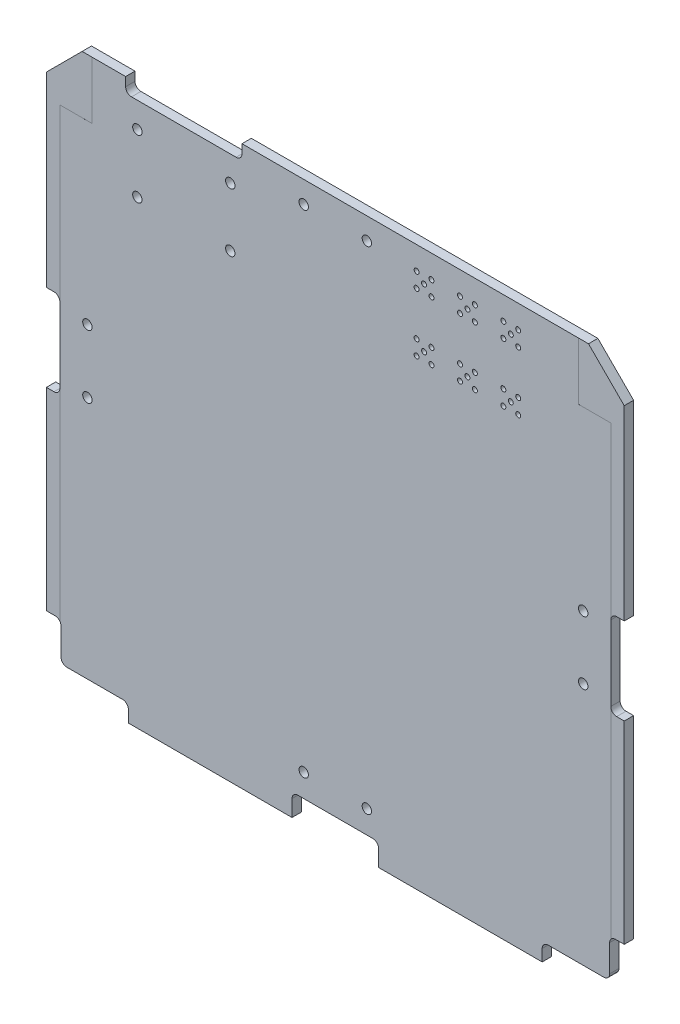
SolidWorks part; units mm, degrees
material "Oshpark board"
ref_plane "Front Plane" through (0, 0, 0) normal (0, 0, 1) x (1, 0, 0)
ref_plane "Top Plane" through (0, 0, 0) normal (0, 1, 0) x (1, 0, 0)
ref_plane "Right Plane" through (0, 0, 0) normal (1, 0, 0) x (0, 0, -1)
ref_plane "Plane4" through (0, 0, -0.0125) normal (0, 0, -1) x (-1, 0, 0)
sketch "Sketch1" plane through (0, 0, -0.0125) normal (0, 0, -1) x (-1, 0, 0)
  line L0 (35.3, -50) -> (35.3, -48)
  line L1 (36.3, -47) -> (45.8, -47)
  line L2 (46.8, -46) -> (46.8, -41.4)
  line L3 (47.8, -40.4) -> (49.3, -40.4)
  line L4 (49.3, -40.4) -> (49.3, 39.2)
  line L5 (49.3, 39.2) -> (43.2, 45.3)
  line L6 (43.2, 45.3) -> (35.5, 45.3)
  line L7 (35.5, 45.3) -> (35.5, 43.8) construction
  line L8 (34.5, 42.8) -> (4.5, 42.8) construction
  line L9 (3.5, 43.8) -> (3.5, 45.3) construction
  line L10 (3.5, 45.3) -> (-43.2, 45.3)
  line L11 (-43.2, 45.3) -> (-49.3, 39.2)
  line L12 (-49.3, 39.2) -> (-49.3, -40.4)
  line L13 (-49.3, -40.4) -> (-47.8, -40.4)
  line L14 (-46.8, -41.4) -> (-46.8, -46)
  line L15 (-45.8, -47) -> (-36.3, -47)
  line L16 (-35.3, -48) -> (-35.3, -50)
  line L17 (-35.3, -50) -> (35.3, -50)
  line L18 (0, -50) -> (0, 45.3) construction
  line L19 (19.5, 42.8) -> (19.5, 25.5258) construction
  line L20 (-13.87, 41.37) -> (-16.41, 38.83) construction
  line L21 (-21.27, 41.37) -> (-23.81, 38.83) construction
  line L22 (-28.67, 41.37) -> (-31.21, 38.83) construction
  line L23 (35.5, 45.3) -> (3.5, 45.3)
  arc A0 (35.3, -48) -> (36.3, -47) centre (36.3, -48) cw
  arc A1 (45.8, -47) -> (46.8, -46) centre (45.8, -46) ccw
  arc A2 (46.8, -41.4) -> (47.8, -40.4) centre (47.8, -41.4) cw
  arc A3 (35.5, 43.8) -> (34.5, 42.8) centre (34.5, 43.8) cw construction
  arc A4 (4.5, 42.8) -> (3.5, 43.8) centre (4.5, 43.8) cw construction
  arc A5 (-47.8, -40.4) -> (-46.8, -41.4) centre (-47.8, -41.4) cw
  arc A6 (-46.8, -46) -> (-45.8, -47) centre (-45.8, -46) ccw
  arc A7 (-36.3, -47) -> (-35.3, -48) centre (-36.3, -48) cw
  circle A8 centre (-21.27, 41.37) radius 0.425
  circle A9 centre (-23.81, 41.37) radius 0.425
  circle A10 centre (-22.54, 40.1) radius 0.425
  circle A11 centre (-13.87, 41.37) radius 0.425
  circle A12 centre (-23.81, 38.83) radius 0.425
  circle A13 centre (-16.41, 41.37) radius 0.425
  circle A14 centre (-15.14, 40.1) radius 0.425
  circle A15 centre (-21.27, 38.83) radius 0.425
  circle A16 centre (-28.67, 41.37) radius 0.425
  circle A17 centre (-31.21, 41.37) radius 0.425
  circle A18 centre (-16.41, 38.83) radius 0.425
  circle A19 centre (-29.94, 40.1) radius 0.425
  circle A20 centre (-31.21, 38.83) radius 0.425
  circle A21 centre (-28.67, 38.83) radius 0.425
  circle A22 centre (33.775, 38.54) radius 0.8 construction
  circle A23 centre (5.225, 38.54) radius 0.8 construction
  circle A24 centre (-13.87, 38.83) radius 0.425
  point P35 (-15.14, 40.1)
  dimension "D7" = 2.5
  dimension "D8" = 1.6
  dimension "D9" = 14.275
  dimension "D10" = 4.26
  dimension "D11" = 1
  dimension "D12" = 1
  dimension "D13" = 1
  dimension "D14" = 1
  dimension "D15" = 1
  dimension "D16" = 1
  dimension "D17" = 1
  dimension "D18" = 1
  dimension "D26" = 0.85
  dimension "D1" = 98.6
  dimension "D2" = 95.3
  dimension "D3" = 14
  dimension "D4" = 9.6
  dimension "D5" = 2.5
  dimension "D6" = 3
  dimension "D19" = 14
  dimension "D20" = 2.5
  dimension "D21" = 6.1
  dimension "D22" = 6.1
  dimension "D23" = 32
  dimension "D24" = 2.54
  dimension "D25" = 2.54
  dimension "D28" = 7.4
  dimension "D29" = 3.93
  dimension "D30" = 35.43
  dimension "D31" = 45
  dimension "D32" = 45
  dimension "D33" = 29.8
  dimension "D34" = 50
  dimension "D27" = 3
extrude "Boss-Extrude1" add sketch "Sketch1" against normal blind 1.6
sketch "thermalContacts_lower" plane through (0, 0, -0.0125) normal (0, 0, -1) x (-1, 0, 0)
  line L3 (47, 35.5) -> (47, -41.5)
  line L4 (41.5, 35.5) -> (41.5, 41.5)
  line L5 (41.5, 35.5) -> (47, 35.5)
  line L9 (-47, 35.5) -> (-47, -41.5)
  line L10 (-41.5, 35.5) -> (-47, 35.5)
  line L11 (-41.5, 35.5) -> (-41.5, 41.5)
  line L14 (-41.5, 41.5) -> (-41.5, 47)
  line L18 (41.5, 41.5) -> (41.5, 47)
  line L19 (-49.3, 39.2) -> (-49.3, -40.4) construction
  line L20 (47, -41.5) -> (59.8273, -41.5)
  line L21 (59.8273, -41.5) -> (59.8273, 47)
  line L22 (-56.1922, 47) -> (-41.5, 47)
  line L23 (41.5, 47) -> (59.8273, 47)
  line L24 (-56.1922, 47) -> (-56.1922, -41.5)
  line L25 (-47, -41.5) -> (-56.1922, -41.5)
  line L26 (49.3, -40.4) -> (49.3, 39.2) construction
  line L27 (-35.3, -50) -> (35.3, -50) construction
  line L28 (43.2, 45.3) -> (-43.2, 45.3) construction
  dimension "D1" = 2.3
  dimension "D2" = 8.5
  dimension "D3" = 1.7
  dimension "D4" = 7.8
  dimension "D5" = 9.8
  dimension "D6" = 8.5
  dimension "D7" = 2.3
  dimension "D8" = 9.8
  dimension "D9" = 7.8
  dimension "D10" = 1.7
sketch "thermalContacts_upper" plane through (0, 0, 1.5875) normal (0, 0, 1) x (1, 0, 0)
  line L3 (-47, 35.5) -> (-47, -41.5)
  line L4 (-41.5, 35.5) -> (-41.5, 41.5)
  line L5 (-41.5, 35.5) -> (-47, 35.5)
  line L9 (47, 35.5) -> (47, -41.5)
  line L10 (41.5, 35.5) -> (47, 35.5)
  line L11 (41.5, 35.5) -> (41.5, 41.5)
  line L14 (41.5, 41.5) -> (41.5, 47)
  line L15 (41.5, 41.5) -> (49.5, 41.5) construction
  line L18 (-41.5, 41.5) -> (-41.5, 47)
  line L19 (-41.5, 41.5) -> (-49.5, 41.5) construction
  line L20 (47, -41.5) -> (59.8273, -41.5)
  line L21 (59.8273, -41.5) -> (59.8273, 47)
  line L22 (59.8273, 47) -> (41.5, 47)
  line L23 (-41.5, 47) -> (-56.1922, 47)
  line L24 (-56.1922, 47) -> (-56.1922, -41.5)
  line L25 (-56.1922, -41.5) -> (-47, -41.5)
pattern_linear "LPattern2" count 2 spacing 10 along (0, -1, 0) of face at (14.295, 41.37, 1.5875) of face at (14.295, 38.83, 1.5875) of face at (15.565, 40.1, 1.5875) of face at (16.835, 38.83, 1.5875) of face at (21.695, 41.37, 1.5875) of face at (21.695, 38.83, 1.5875) of face at (22.965, 40.1, 1.5875) of face at (24.235, 38.83, 1.5875) of face at (24.235, 41.37, 1.5875) of face at (16.835, 41.37, 1.5875) of face at (29.095, 41.37, 1.5875) of face at (29.095, 38.83, 1.5875) of face at (30.365, 40.1, 1.5875) of face at (31.635, 38.83, 1.5875) of face at (31.635, 41.37, 1.5875)
extrude "slotFootprints_REF" cut sketch "thermalContacts_lower" against normal blind 0.0001
extrude "slotFootprints" cut sketch "thermalContacts_upper" against normal blind 0.0001
sketch "Sketch2" plane through (0, 0, 1.5875) normal (0, 0, 1) x (1, 0, 0)
  line L1 (-41.5, 45.3) -> (41.5, 45.3) construction
  line L2 (-49.3, -40.4) -> (-49.3, 39.2) construction
  line L3 (-35.775, 45.3) -> (-35.775, 43.8)
  line L4 (-41.5, 45.3) -> (41.5, 45.3) construction
  line L5 (-34.775, 42.8) -> (-16.925, 42.8)
  line L6 (-15.925, 43.8) -> (-15.925, 45.3)
  line L7 (-15.925, 45.3) -> (-35.775, 45.3)
  arc A1 (-16.925, 42.8) -> (-15.925, 43.8) centre (-16.925, 43.8) ccw
  arc A2 (-35.775, 43.8) -> (-34.775, 42.8) centre (-34.775, 43.8) ccw
  circle A3 centre (-33.775, 38.4723) radius 0.8
  circle A4 centre (-17.925, 38.4723) radius 0.8
  circle A5 centre (-17.925, 28.4723) radius 0.8
  circle A6 centre (-33.775, 28.4723) radius 0.8
  dimension "D2" = 1.6
  dimension "D5" = 1
  dimension "D1" = 15.85
  dimension "D3" = 6.8277
  dimension "D4" = 15.525
  dimension "D6" = 2
  dimension "D7" = 2
  dimension "D8" = 2.5
  dimension "D10" = 10
  dimension "D9" = 2
extrude "20pin_mounts" cut sketch "Sketch2" against normal through all
sketch "Sketch3" plane through (0, 0, -0.0125) normal (0, 0, -1) x (-1, 0, 0)
  line L0 (-49.3, -40.4) -> (-49.3, 39.2) construction
  line L1 (5.39, 41.6) -> (-5.38, 41.6) construction
  line L2 (42.3, -5.39) -> (42.3, 5.38) construction
  line L3 (15.925, 45.3) -> (-41.5, 45.3) construction
  line L4 (5.39, -42.3032) -> (-5.38, -42.3032) construction
  line L5 (-42.3, -5.39) -> (-42.3, 5.38) construction
  line L6 (41.5, 45.3) -> (35.775, 45.3) construction
  line L7 (42.3, -0.005) -> (-42.3, -0.005) construction
  line L8 (0.005, -42.3032) -> (0.005, 41.6) construction
  line L9 (49.3, -40.4) -> (49.3, 39.2) construction
  line L10 (-35.3, -50) -> (35.3, -50) construction
  line L11 (-42.3, -0.005) -> (-49.3, -0.005) construction
  line L12 (42.3, -0.005) -> (49.3, -0.005) construction
  line L13 (49.3, -40.4) -> (49.3, 39.2) construction
  line L14 (-49.3, 7.38) -> (-48, 7.38)
  line L15 (-47, 6.38) -> (-47, -6.39)
  line L16 (-48, -7.39) -> (-49.3, -7.39)
  line L17 (-49.3, -7.39) -> (-49.3, 7.38)
  line L18 (-49.3, -40.4) -> (-49.3, 39.2) construction
  line L19 (-47, 35.5) -> (-47, -40.8) construction
  line L20 (47, -40.8) -> (47, 35.5) construction
  line L21 (48, 7.38) -> (49.3, 7.38)
  line L22 (47, 6.38) -> (47, -6.39)
  line L23 (48, -7.39) -> (49.3, -7.39)
  line L24 (49.3, 7.38) -> (49.3, -7.39)
  line L26 (-6.38, -46.2032) -> (6.39, -46.2032)
  line L27 (-7.38, -47.2032) -> (-7.38, -50)
  line L28 (-7.38, -50) -> (7.39, -50)
  line L29 (7.39, -47.2032) -> (7.39, -50)
  arc A0 (-47, -6.39) -> (-48, -7.39) centre (-48, -6.39) cw
  arc A1 (-48, 7.38) -> (-47, 6.38) centre (-48, 6.38) cw
  circle A2 centre (5.39, 41.6) radius 0.8
  circle A3 centre (-5.38, 41.6) radius 0.8
  arc A4 (47, -6.39) -> (48, -7.39) centre (48, -6.39) ccw
  arc A5 (48, 7.38) -> (47, 6.38) centre (48, 6.38) ccw
  arc A6 (-6.38, -46.2032) -> (-7.38, -47.2032) centre (-6.38, -47.2032) ccw
  circle A7 centre (42.3, 5.38) radius 0.8
  circle A8 centre (42.3, -5.39) radius 0.8
  circle A9 centre (5.39, -42.3032) radius 0.8
  circle A10 centre (-5.38, -42.3032) radius 0.8
  circle A11 centre (-42.3, -5.39) radius 0.8
  circle A12 centre (-42.3, 5.38) radius 0.8
  arc A13 (6.39, -46.2032) -> (7.39, -47.2032) centre (6.39, -47.2032) cw
  point P16 (-47, -0.005)
  point P51 (47, -0.005)
  point P63 (0.005, -46.2032)
  dimension "D1" = 1.6
  dimension "D5" = 39.92
  dimension "D6" = 7
  dimension "D9" = 1
  dimension "D11" = 1
  dimension "D14" = 1
  dimension "D2" = 10.77
  dimension "D3" = 43.92
  dimension "D4" = 3.7
  dimension "D7" = 7.6968
  dimension "D8" = 2
  dimension "D10" = 2
  dimension "D12" = 3.9
  dimension "D13" = 2
extrude "12pin_mounts" cut sketch "Sketch3" against normal blind 10
